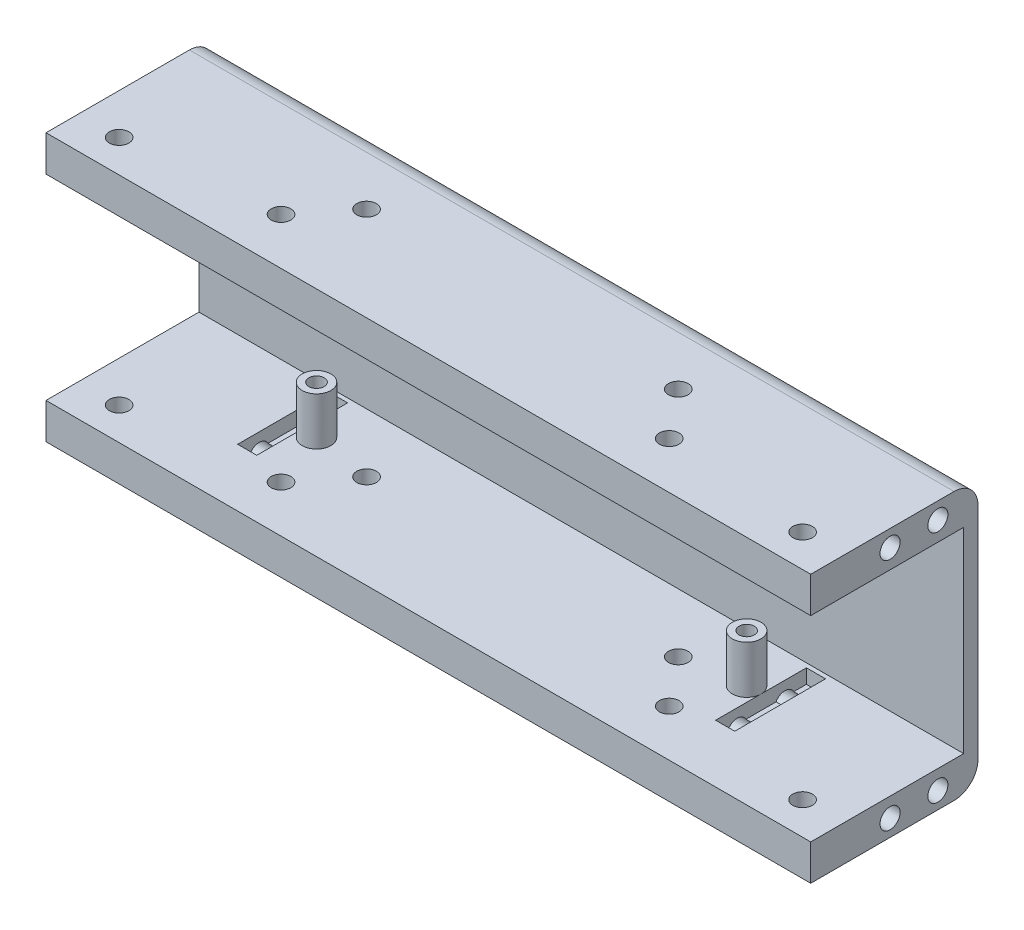
SolidWorks part; units mm, degrees
material "petg 20%"
ref_plane "Front Plane" through (0, 0, 0) normal (0, 0, 1) x (1, 0, 0)
ref_plane "Top Plane" through (0, 0, 0) normal (0, 1, 0) x (1, 0, 0)
ref_plane "Right Plane" through (0, 0, 0) normal (1, 0, 0) x (0, 0, -1)
sketch "Sketch1" plane through (0, 0, 0) normal (0, 0, 1) x (1, 0, 0)
  line L1 (-80, 28) -> (80, 28)
  line L2 (-80, 28) -> (-80, -28)
  line L3 (-80, -28) -> (80, -28)
  line L4 (80, 28) -> (80, -28)
  line L5 (-80, 28) -> (80, -28) construction
  line L6 (-80, -28) -> (80, 28) construction
  point P0 (0, 0)
  dimension "D1" = 160
  dimension "D2" = 56
extrude "Boss-Extrude1" add sketch "Sketch1" along normal blind 35
sketch "Sketch2" plane through (-80, 0, 0) normal (-1, 0, 0) x (0, 0, 1)
  line L0 (35, 28) -> (0, 28) construction
  line L1 (3, 20.5) -> (35, 20.5)
  line L2 (3, 20.5) -> (3, -20.5)
  line L3 (3, -20.5) -> (35, -20.5)
  line L4 (35, 20.5) -> (35, -20.5)
  line L5 (35, -28) -> (0, -28) construction
  line L6 (35, 28) -> (35, -28) construction
  line L7 (0, 28) -> (0, -28) construction
  dimension "D1" = 7.5
  dimension "D2" = 7.5
  dimension "D3" = 3
extrude "Cut-Extrude1" cut sketch "Sketch2" against normal through all
fillet "Fillet1" radius 5 2 edges at (0, -28, 0) (0, 28, 0)
sketch "Sketch6" plane through (0, 20.5, 0) normal (0, -1, 0) x (1, 0, 0)
  line L0 (-52, 22.9) -> (-52, 3.9)
  line L1 (-52, 22.9) -> (-48, 22.9)
  line L2 (-52, 3.9) -> (-48, 3.9)
  line L3 (-48, 22.9) -> (-48, 3.9)
  line L4 (80, 0) -> (-80, 0) construction
  line L5 (-80, 35) -> (-80, 3) construction
  dimension "D1" = 3.9
  dimension "D2" = 19
  dimension "D3" = 4
  dimension "D4" = 28
extrude "Cut-Extrude4" cut sketch "Sketch6" against normal blind 3
ref_plane "Plane1" through (0, 0, 0) normal (-1, 0, 0) x (0, 0, 1)
ref_plane "Plane2" through (0, 0, 0) normal (0, 1, 0) x (1, 0, 0)
mirror "Mirror3" about plane through (0, 0, 0) normal (-1, 0, 0) of "Cut-Extrude4"
mirror "Mirror4" about plane through (0, 0, 0) normal (0, 1, 0) of "Mirror3"
sketch "Sketch8" plane through (-80, 0, 0) normal (-1, 0, 0) x (0, 0, 1)
  line L0 (35, -28) -> (5, -28) construction
  circle A1 centre (18.4, -24.5) radius 2.1
  circle A2 centre (8.4, -24.5) radius 2.1
  dimension "D1" = 4.2
  dimension "D2" = 4.2
  dimension "D3" = 3.5
  dimension "D4" = 10
extrude "Cut-Extrude6" cut sketch "Sketch8" against normal through all
mirror "Mirror5" about plane through (0, 0, 0) normal (0, 1, 0) of "Cut-Extrude6"
sketch "Sketch10" plane through (0, -20.5, 0) normal (0, 1, 0) x (1, 0, 0)
  line L0 (0, 0) -> (0, -37.1263) construction
  line L1 (0, 19.25) -> (0, -19.25) construction
  line L2 (80, -35) -> (-80, -35) construction
  circle A0 centre (-45, -13.4) radius 1.5
  circle A1 centre (-45, -13.4) radius 3
  dimension "D1" = 45
  dimension "D2" = 21.6
  dimension "D3" = 3
  dimension "D4" = 6
extrude "Boss-Extrude3" add sketch "Sketch10" along normal blind 10
sketch "Sketch13" plane through (0, -10.5, 0) normal (0, 1, 0) x (1, 0, 0)
  line L0 (80, -35) -> (-80, -35) construction
  line L1 (0, 19.25) -> (0, -19.25) construction
  circle A0 centre (-45, -13.4) radius 1.6
  dimension "D1" = 21.6
  dimension "D2" = 45
  dimension "D3" = 3.2
extrude "Cut-Extrude9" cut sketch "Sketch13" against normal through all
mirror "Mirror6" about plane through (0, 0, 0) normal (-1, 0, 0) of "Boss-Extrude3", "Cut-Extrude9"
sketch "Sketch14" plane through (0, 28, 0) normal (0, 1, 0) x (1, 0, 0)
  circle A0 centre (-71.5036, -28.2033) radius 2.05
  circle A1 centre (-40.6101, -25.2161) radius 2.05
  circle A2 centre (-32.6101, -15.32) radius 2.05
  circle A3 centre (71.5036, -28.2033) radius 2.05
  circle A4 centre (40.6101, -25.2161) radius 2.05
  circle A5 centre (32.6101, -15.32) radius 2.05
  circle A6 centre (40.6101, -91.5839) radius 2.05
  circle A7 centre (71.5036, -88.5967) radius 2.05
  circle A8 centre (32.6101, -101.48) radius 2.05
  circle A9 centre (-32.6101, -101.48) radius 2.05
  circle A10 centre (-40.6101, -91.5839) radius 2.05
  circle A11 centre (-71.5036, -88.5967) radius 2.05
extrude "Cut-Extrude10" cut sketch "Sketch14" against normal through all
